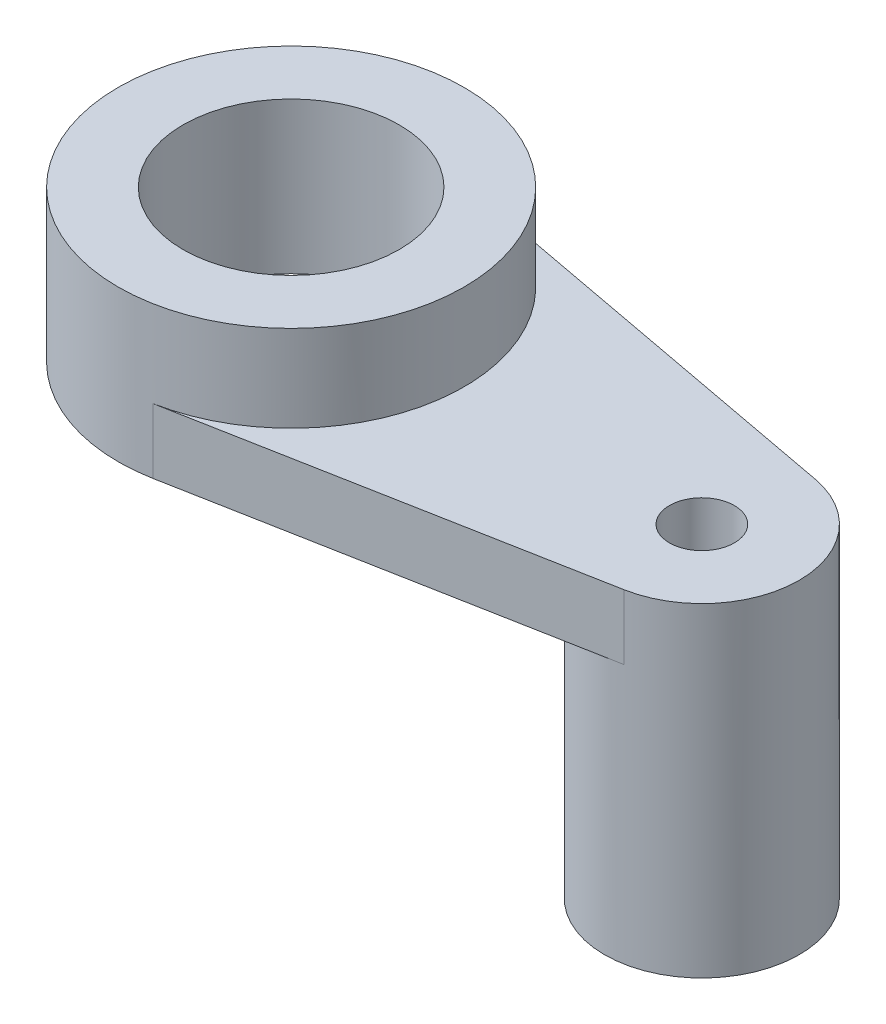
SolidWorks part; units mm, degrees
material "Galvanized Steel"
ref_plane "Front Plane" through (0, 0, 0) normal (0, 0, 1) x (1, 0, 0)
ref_plane "Top Plane" through (0, 0, 0) normal (0, 1, 0) x (1, 0, 0)
ref_plane "Right Plane" through (0, 0, 0) normal (1, 0, 0) x (0, 0, -1)
sketch "Sketch1" plane through (0, 0, 0) normal (0, 1, 0) x (1, 0, 0)
  line L0 (39.6579, 8.846) -> (2.9474, 15.7262)
  line L1 (39.6579, -8.846) -> (2.9474, -15.7262)
  circle A0 centre (0, 0) radius 16
  circle A1 centre (38, 0) radius 9
  circle A2 centre (0, 0) radius 10
  circle A3 centre (38, 0) radius 3
  point P11 (0, 0)
  dimension "D1" = 20
  dimension "D2" = 6
  dimension "D3" = 6
  dimension "D4" = 18
  dimension "D5" = 38
extrude "Boss-Extrude1" add sketch "Sketch1" along normal blind 6 contours A0 A2 | A1 L0 A0 L1 | A1 A3 region at (21.925, 0, 0) region at (44.7295, 0, -5.5854) region at (11.9635, 0, -9.9296)
extrude "Boss-Extrude2" add sketch "Sketch1<3>" along normal blind 14 contours A0 A2 region at (11.9635, 0, -9.9296)
sketch "Sketch1<3>" plane through (0, 0, 0) normal (0, 1, 0) x (1, 0, 0) same geometry as "Sketch1"
extrude "Boss-Extrude3" add sketch "Sketch1<4>" against normal blind 24 contours A1 A3 region at (44.7295, 0, -5.5854)
sketch "Sketch1<4>" plane through (0, 0, 0) normal (0, 1, 0) x (1, 0, 0) same geometry as "Sketch1"
